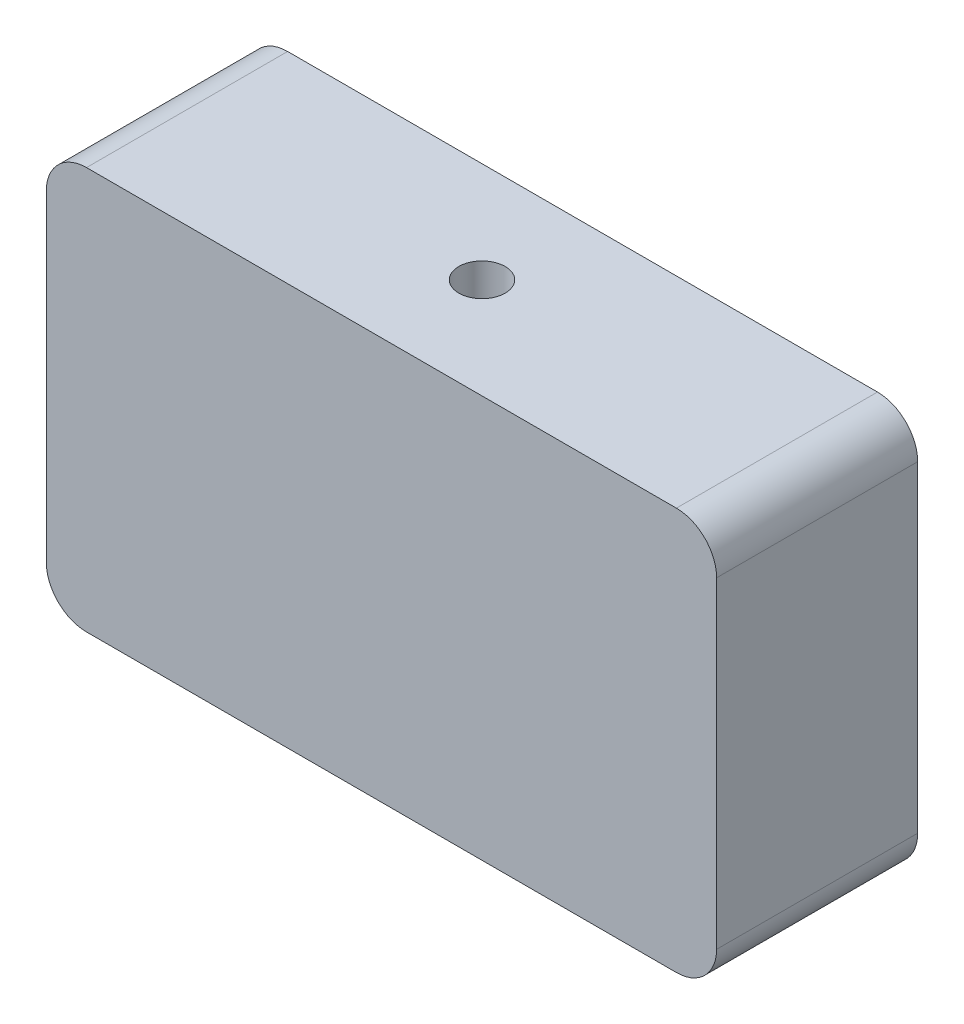
SolidWorks part; units mm, degrees
ref_plane "Front Plane" through (0, 0, 0) normal (0, 0, 1) x (1, 0, 0)
ref_plane "Top Plane" through (0, 0, 0) normal (0, 1, 0) x (1, 0, 0)
ref_plane "Right Plane" through (0, 0, 0) normal (1, 0, 0) x (0, 0, -1)
sketch "Sketch2" plane through (0, 0, 0) normal (0, 0, 1) x (1, 0, 0)
  line L1 (-25, -15) -> (25, -15)
  line L2 (-25, -15) -> (-25, 15)
  line L3 (-25, 15) -> (25, 15)
  line L4 (25, -15) -> (25, 15)
  line L5 (-25, -15) -> (25, 15) construction
  line L6 (-25, 15) -> (25, -15) construction
  circle A0 centre (20, 10) radius 3.35
  circle A1 centre (-20, 10) radius 3.35
  circle A2 centre (-20, -10) radius 3.35
  circle A3 centre (20, -10) radius 3.35
  point P0 (0, 0)
  dimension "D3" = 20
  dimension "D1" = 30
  dimension "D2" = 50
  dimension "D4" = 10
extrude "Boss-Extrude1" add sketch "Sketch2" along normal blind 15 contours L3 L4 L1 L2
sketch "Sketch7" plane through (0, 15, 0) normal (0, 1, 0) x (1, 0, 0)
  line L0 (0, 0) -> (0, -15) construction
  line L1 (25, 0) -> (-25, 0) construction
  line L2 (25, -15) -> (-25, -15) construction
  point P6 (0, -7.5)
sketch "Sketch8" plane through (0, 0, 0) normal (0, 0, -1) x (-1, 0, 0)
  line L0 (25, -15) -> (-25, 15) construction
  line L1 (25, 15) -> (-25, -15) construction
  point P4 (0, 0)
  point P8 (0, 0)
hole_wizard "#8-32 Tapped Hole1" positions "3DSketch1" profile "Sketch9" tap size "#8-32" standard "ANSI Inch"
sketch3d "3DSketch1"
  point P0 (0, 15, 7.5)
sketch "Sketch9" plane through (0, 15, 7.5) normal (1, 0, 0) x (0, 0, 1)
  line L0 (0, 0) -> (0, 6.0378)
  line L1 (0, 6.0378) -> (1.7272, 5)
  line L2 (1.7272, 5) -> (1.7272, 0)
  line L5 (1.7272, 0) -> (0, 0)
  line L10 (0, 6.0378) -> (-1.7272, 5) construction
  line L11 (0, -6.35) -> (0, 107.95) construction
  dimension "Tap Drill Dia." = 3.4544
  dimension "Tap Drill Depth" = 5
  dimension "Drill Angle" = 118
fillet "Fillet1" radius 3 1 edges at (25, 15, 7.5)
fillet "Fillet2" radius 3 1 edges at (-25, 15, 7.5)
fillet "Fillet3" radius 3 1 edges at (25, -15, 7.5)
fillet "Fillet4" radius 3 1 edges at (-25, -15, 7.5)
